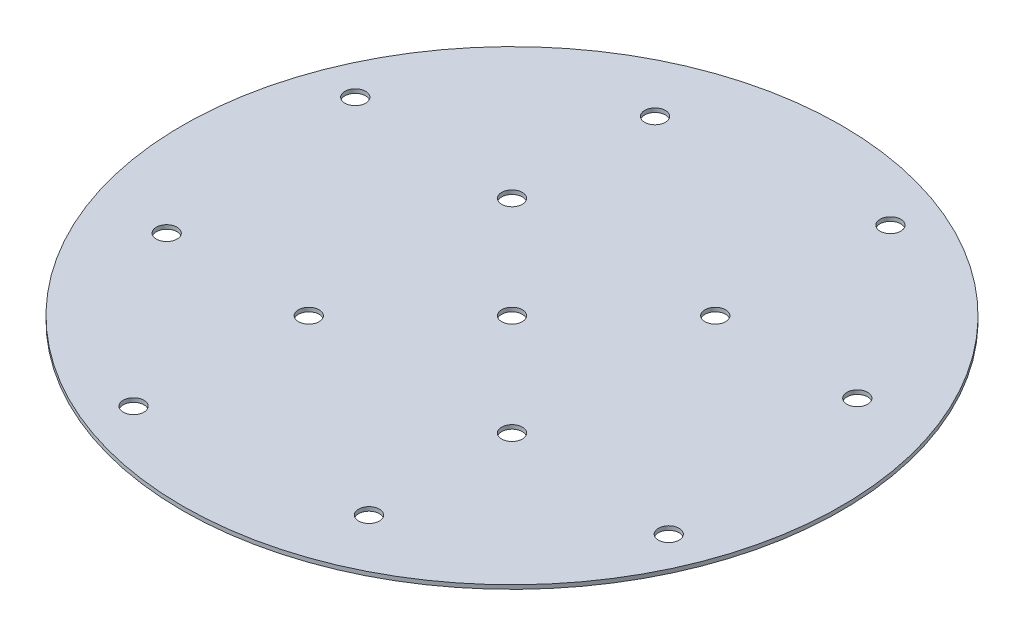
SolidWorks part; units mm, degrees
material "6061-T6 (SS)"
ref_plane "Front Plane" through (0, 0, 0) normal (0, 0, 1) x (1, 0, 0)
ref_plane "Top Plane" through (0, 0, 0) normal (0, 1, 0) x (1, 0, 0)
ref_plane "Right Plane" through (0, 0, 0) normal (1, 0, 0) x (0, 0, -1)
sketch "Sketch2" plane through (0, 0, 0) normal (1, 0, 0) x (0, 0, -1)
  line L0 (0, 0) -> (-82.55, 0)
  line L1 (-82.55, 0) -> (-82.55, 1)
  line L2 (-82.55, 1) -> (0, 1)
  line L5 (0, 1) -> (0, 0)
  dimension "D1" = 82.55
  dimension "D2" = 1
ref_axis "Axis1" through (0, -0.05, 0) along (0, 1, 0)
revolve "Revolve1" add sketch "Sketch2" angle 360 about axis through (0, -0.05, 0) along (0, 1, 0)
hole_wizard "#6 (0.204) Diameter Hole1" positions "Sketch6" profile "Sketch7" hole size "#6" standard "ANSI Inch" end condition through all
sketch "Sketch6" plane through (0, 1, 0) normal (0, 1, 0) x (1, 0, 0)
  line L0 (0, 0) -> (-53.438, 129.0108) construction
  line L2 (0, 0) -> (0, 109.0908) construction
  line L3 (0, 0) -> (-76.2663, 31.5905) construction
  line L4 (0, 0) -> (-47.7784, 47.7784) construction
  circle A0 centre (0, 0) radius 82.55 construction
  point P0 (-25.3336, 61.1608)
  point P11 (264.7437, 73.7878)
  point P20 (-67.0275, 27.7637)
  point P22 (-25.4558, 25.4558)
  dimension "D1" = 22.5
  dimension "D2" = 66.2
  dimension "D3" = 72.55
  dimension "D4" = 45
  dimension "D6" = 22.5
  dimension "D5" = 36
sketch "Sketch7" plane through (-25.3336, 1, -61.1608) normal (1, 0, 0) x (0, 0, 1)
  line L0 (0, 0) -> (0, 1)
  line L1 (0, 1) -> (2.5908, 1)
  line L2 (2.5908, 1) -> (2.5908, 0)
  line L5 (2.5908, 0) -> (0, 0)
  line L11 (0, -6.35) -> (0, 107.95) construction
  dimension "Thru Hole Dia." = 5.1816
  dimension "Thru Hole Depth" = 1
pattern_circular "CirPattern3" count 4 over 360 about axis through (0, -0.05, 0) along (0, 1, 0) of "#6 (0.204) Diameter Hole1"
hole_wizard "#6 (0.204) Diameter Hole2" positions "Sketch8" profile "Sketch9" hole size "#6" standard "ANSI Inch" end condition through all
sketch "Sketch8" plane through (0, 1, 0) normal (0, 1, 0) x (1, 0, 0)
  line L0 (0, 0) -> (106.3094, -1.7118) construction
  point P7 (0, 0)
sketch "Sketch9" plane through (0, 1, 0) normal (1, 0, 0) x (0, 0, 1)
  line L0 (0, 0) -> (0, 1)
  line L1 (0, 1) -> (2.5908, 1)
  line L2 (2.5908, 1) -> (2.5908, 0)
  line L5 (2.5908, 0) -> (0, 0)
  line L11 (0, -6.35) -> (0, 107.95) construction
  dimension "Thru Hole Dia." = 5.1816
  dimension "Thru Hole Depth" = 1
equation "\"TubeDiameter\" = 6.500in"
equation "\"D1@Sketch2\"=\"TubeDiameter\"/2"
equation "\"D2@Sketch6\"=66.2"
equation "\"D3@Sketch6\"=\"TubeDiameter\"/2-10mm"
